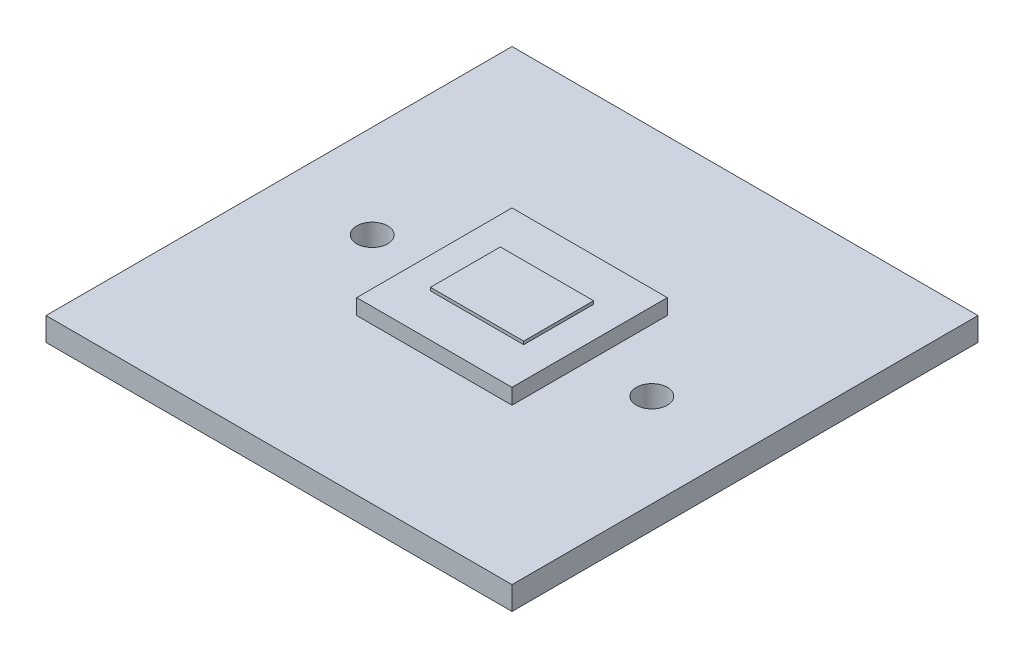
SolidWorks part; units mm, degrees
ref_plane "前视基准面" through (0, 0, 0) normal (0, 0, 1) x (1, 0, 0)
ref_plane "上视基准面" through (0, 0, 0) normal (0, 1, 0) x (1, 0, 0)
ref_plane "右视基准面" through (0, 0, 0) normal (1, 0, 0) x (0, 0, -1)
sketch "草图1" plane through (0, 0, 0) normal (0, 1, 0) x (1, 0, 0)
  line L1 (-5, -5) -> (5, -5)
  line L2 (-5, -5) -> (-5, 5)
  line L3 (-5, 5) -> (5, 5)
  line L4 (5, -5) -> (5, 5)
  line L5 (-5, -5) -> (5, 5) construction
  line L6 (-5, 5) -> (5, -5) construction
  point P0 (0, 0)
  dimension "D1" = 10
  dimension "D2" = 10
extrude "凸台-拉伸1" add sketch "草图1" along normal blind 1
sketch "草图2" plane through (0, 1, 0) normal (0, 1, 0) x (1, 0, 0)
  line L1 (-3, -2.25) -> (3, -2.25)
  line L2 (-3, -2.25) -> (-3, 2.25)
  line L3 (-3, 2.25) -> (3, 2.25)
  line L4 (3, -2.25) -> (3, 2.25)
  line L5 (-3, -2.25) -> (3, 2.25) construction
  line L6 (-3, 2.25) -> (3, -2.25) construction
  point P0 (0, 0)
  dimension "D1" = 6
  dimension "D2" = 4.5
extrude "凸台-拉伸2" add sketch "草图2" along normal blind 0.2
sketch "草图3" plane through (0, 0, 0) normal (0, -1, 0) x (1, 0, 0)
  line L1 (-15, 15) -> (15, 15)
  line L2 (-15, 15) -> (-15, -15)
  line L3 (-15, -15) -> (15, -15)
  line L4 (15, 15) -> (15, -15)
  line L5 (-15, 15) -> (15, -15) construction
  line L6 (-15, -15) -> (15, 15) construction
  point P0 (0, 0)
  dimension "D1" = 30
  dimension "D2" = 30
extrude "凸台-拉伸3" add sketch "草图3" along normal blind 1.5
sketch "草图4" plane through (0, 0, 0) normal (0, 1, 0) x (1, 0, 0)
  line L0 (5, -5) -> (5, 5) construction
  line L1 (-5, 5) -> (-5, -5) construction
  circle A0 centre (9, 0) radius 1
  circle A1 centre (-9, 0) radius 1
  dimension "D1" = 4
  dimension "D2" = 4
extrude "切除-拉伸2" cut sketch "草图4" against normal through all
ref_axis "基准轴1" through (0, 0, 0) along (0, 1, 0)
